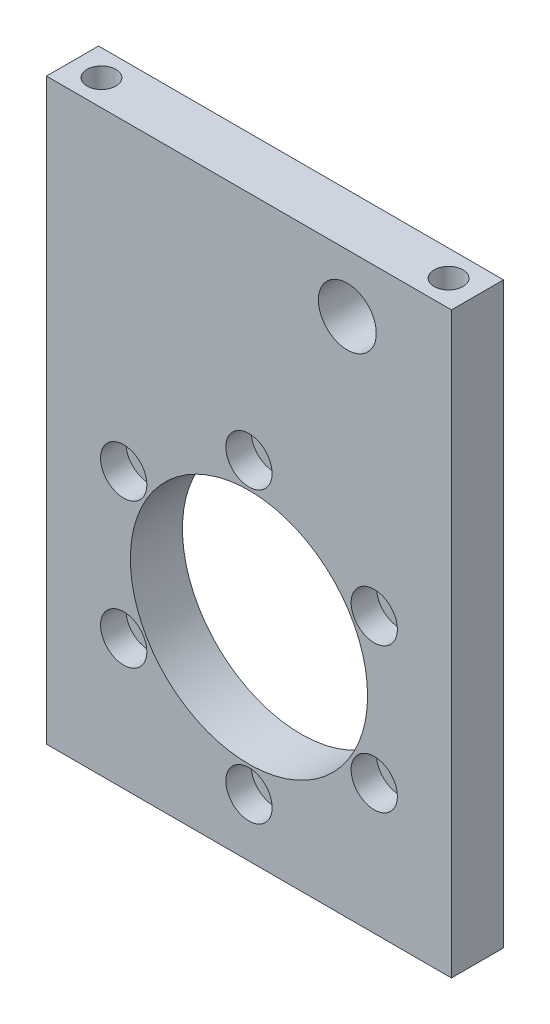
SolidWorks part; units mm, degrees
material "1060 Alloy"
ref_plane "Front Plane" through (0, 0, 0) normal (0, 0, 1) x (1, 0, 0)
ref_plane "Top Plane" through (0, 0, 0) normal (0, 1, 0) x (1, 0, 0)
ref_plane "Right Plane" through (0, 0, 0) normal (1, 0, 0) x (0, 0, -1)
sketch "Sketch1" plane through (0, 0, 0) normal (0, 0, 1) x (1, 0, 0)
  line L1 (0, 0) -> (70, 0)
  line L2 (0, 0) -> (0, 100)
  line L3 (0, 100) -> (70, 100)
  line L4 (70, 0) -> (70, 100)
  dimension "D1" = 70
  dimension "D2" = 100
extrude "Boss-Extrude1" add sketch "Sketch1" along normal mid plane 9
sketch "Sketch3" plane through (0, 0, 0) normal (0, 0, 1) x (1, 0, 0)
  circle A0 centre (35, 35) radius 20.5
  dimension "D1" = 41
  dimension "D2" = 35
  dimension "D3" = 35
extrude "Cut-Extrude2" cut sketch "Sketch3" against normal through all both and the other way through all
hole_wizard "M6 Tapped Hole1" positions "Sketch4" profile "Sketch5" tap size "M6" standard "ISO"
sketch "Sketch4" plane through (0, 0, 0) normal (0, -1, 0) x (-1, 0, 0)
  line L0 (-70, -4.5) -> (-70, 4.5) construction
  line L1 (0, -4.5) -> (0, 4.5) construction
  point P0 (-65, 0)
  point P2 (-5, 0)
  dimension "D1" = 5
  dimension "D2" = 5
sketch "Sketch5" plane through (65, 0, 0) normal (1, 0, 0) x (0, 0, -1)
  line L0 (0, 0) -> (0, 16.5022)
  line L1 (0, 16.5022) -> (2.5, 15)
  line L2 (2.5, 15) -> (2.5, 0)
  line L5 (2.5, 0) -> (0, 0)
  line L10 (0, 16.5022) -> (-2.5, 15) construction
  line L11 (0, -6.35) -> (0, 107.95) construction
  dimension "Tap Drill Dia." = 5
  dimension "Tap Drill Depth" = 15
  dimension "Drill Angle" = 118
cosmetic thread "Hole Thread1" parameters "D1"=12, "D2"=6
cosmetic thread "Hole Thread2" parameters "D1"=12, "D2"=6
ref_plane "Plane1" through (0, 50, 0) normal (0, 1, 0) x (1, 0, 0)
mirror "Mirror1" about plane through (0, 50, 0) normal (0, 1, 0) of "M6 Tapped Hole1"
hole_wizard "CBORE for M4 Hex Socket Head Cap Screw1" positions "Sketch6" profile "Sketch7" counterbore size "M4" standard "ISO" end condition through all
sketch "Sketch6" plane through (0, 0, 4.5) normal (0, 0, 1) x (1, 0, 0)
  line L0 (14.5, 35) -> (55.5, 35) construction
  circle A0 centre (35, 35) radius 20.5 construction
  point P0 (35, 60)
  point P16 (35, 35)
  dimension "D1" = 25
sketch "Sketch7" plane through (35, 60, 4.5) normal (1, 0, 0) x (0, -1, 0)
  line L0 (0, 0) -> (0, 9)
  line L1 (0, 9) -> (2.15, 9)
  line L3 (2.15, 9) -> (2.15, 4.4)
  line L4 (2.15, 4.4) -> (4, 4.4)
  line L5 (4, 4.4) -> (4, 0)
  line L7 (4, 0) -> (0, 0)
  line L11 (0, -6.35) -> (0, 107.95) construction
  dimension "Thru Hole Dia." = 4.3
  dimension "Thru Hole Depth" = 9
  dimension "C'Bore Dia." = 8
  dimension "C'Bore Depth" = 4.4
pattern_circular "CirPattern1" count 6 over 360 about axis through (35, 35, -4.5) along (0, 0, 1) of "CBORE for M4 Hex Socket Head Cap Screw1"
sketch "Sketch8" plane through (0, 0, 4.5) normal (0, 0, 1) x (1, 0, 0)
  line L0 (70, 100) -> (0, 100) construction
  line L1 (70, 0) -> (70, 100) construction
  circle A0 centre (52, 90) radius 5
  dimension "D1" = 10
  dimension "D2" = 10
  dimension "D3" = 18
extrude "Cut-Extrude3" cut sketch "Sketch8" against normal blind 10
move or copy body "Body-Move/Copy1" [suppressed] bodies to move or copy 113
